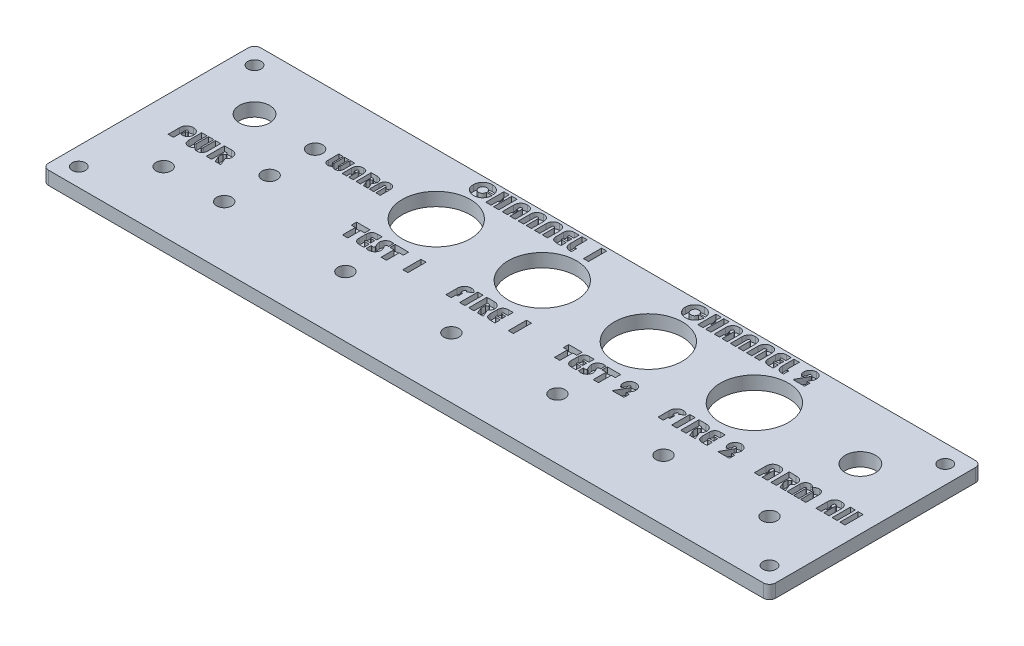
SolidWorks part; units mm, degrees
ref_plane "Front Plane" through (0, 0, 0) normal (0, 0, 1) x (1, 0, 0)
ref_plane "Top Plane" through (0, 0, 0) normal (0, 1, 0) x (1, 0, 0)
ref_plane "Right Plane" through (0, 0, 0) normal (1, 0, 0) x (0, 0, -1)
sketch "face" plane through (0, 0, 0) normal (0, 1, 0) x (1, 0, 0)
  line L0 (152.4, 88.9) -> (152.4, 0) construction
  line L1 (0, 0) -> (304.8, 0)
  line L2 (0, 0) -> (0, 88.9)
  line L3 (0, 88.9) -> (304.8, 88.9)
  line L4 (304.8, 0) -> (304.8, 88.9)
  line L5 (0, 44.45) -> (304.8, 44.45) construction
  line L6 (234.95, 63.5) -> (234.95, 25.4) construction
  line L7 (25.4, 63.5) -> (25.4, 25.4) construction
  line L8 (279.4, 63.5) -> (279.4, 25.4) construction
  line L12 (279.4, 63.5) -> (234.95, 63.5) construction
  line L13 (279.4, 63.5) -> (25.4, 63.5) construction
  line L14 (50.8, 63.5) -> (50.8, 25.4) construction
  circle A0 centre (7.62, 81.28) radius 2.794
  circle A12 centre (297.18, 81.28) radius 2.794
  circle A13 centre (297.18, 7.62) radius 2.794
  circle A14 centre (7.62, 7.62) radius 2.794
  circle A26 centre (234.95, 63.5) radius 14.2875
  circle A31 centre (234.95, 25.4) radius 3.175
  circle A40 centre (279.4, 63.5) radius 6.35
  circle A41 centre (279.4, 25.4) radius 3.175
  circle A45 centre (25.4, 63.5) radius 6.35
  circle A46 centre (25.4, 25.4) radius 3.175
  circle A48 centre (190.5, 63.5) radius 14.2875
  circle A49 centre (190.5, 25.4) radius 3.175
  circle A50 centre (146.05, 63.5) radius 14.2875
  circle A51 centre (146.05, 25.4) radius 3.175
  circle A52 centre (101.6, 63.5) radius 14.2875
  circle A53 centre (101.6, 25.4) radius 3.175
  circle A54 centre (50.8, 63.5) radius 3.175
  circle A55 centre (50.8, 25.4) radius 3.175
  circle A56 centre (50.8, 44.45) radius 3.175
  point P11 (279.4, 44.45)
  point P22 (25.4, 44.45)
  dimension "D3" = 5.588
  dimension "D6" = 12.7
  dimension "D7" = 6.35
  dimension "D11" = 44.45
  dimension "D16" = 28.575
  dimension "D21" = 6.35
  dimension "D9" = 25.4
  dimension "D12" = 6.35
  dimension "D13" = 12.7
  dimension "D14" = 6.35
  dimension "D18" = 6.35
  dimension "D19" = 6.35
  dimension "D1" = 304.8
  dimension "D2" = 88.9
  dimension "D4" = 7.62
  dimension "D5" = 7.62
  dimension "D8" = 38.1
  dimension "D10" = 44.45
  dimension "D15" = 25.4
  dimension "D17" = 25.4
extrude "face_cut" add sketch "face" along normal blind 5.588 contours L1 L4 L3 L2 A12 A40 A41 A0 A13 A14 region at (151.0156, 0, -42.3544)
fillet "Fillet1" radius 2.54 4 edges at (0, 2.794, -88.9) (0, 2.794, 0) (304.8, 2.794, 0) (304.8, 2.794, -88.9)
sketch "Sketch1" plane through (0, 5.588, 0) normal (0, 1, 0) x (1, 0, 0)
  line L0 (92.075, 80.01) -> (155.575, 80.01) construction
  line L1 (146.05, 63.5) -> (101.6, 63.5) construction
  line L2 (123.825, 63.5) -> (123.825, 80.01) construction
  line L3 (234.95, 63.5) -> (190.5, 63.5) construction
  line L4 (212.725, 63.5) -> (212.725, 80.01) construction
  line L5 (180.975, 80.01) -> (244.475, 80.01) construction
  line L6 (279.4, 63.5) -> (279.4, 38.1) construction
  line L7 (259.3255, 38.1) -> (299.4745, 38.1) construction
  line L8 (82.55, 38.1) -> (120.65, 38.1) construction
  line L9 (101.6, 63.5) -> (101.6, 38.1) construction
  line L10 (127, 38.1) -> (165.1, 38.1) construction
  line L11 (146.05, 63.5) -> (146.05, 38.1) construction
  line L12 (171.45, 38.1) -> (209.55, 38.1) construction
  line L13 (190.5, 63.5) -> (190.5, 38.1) construction
  line L14 (234.95, 63.5) -> (234.95, 38.1) construction
  line L15 (215.9, 38.1) -> (254, 38.1) construction
  line L16 (0, 38.1) -> (50.8, 38.1) construction
  line L17 (25.4, 63.5) -> (25.4, 38.1) construction
  line L18 (56.3957, 60.365) -> (82.55, 60.365) construction
  text T0 "CHANNEL 1" font "Blippo" height 7.62
  text T1 "CHANNEL 2" font "Blippo" height 7.62
  text T2 "ARM All" font "Blippo" height 7.62
  text T3 "TEST 1" font "Blippo" height 7.62
  text T4 "FIRE 1" font "Blippo" height 7.62
  text T5 "TEST 2" font "Blippo" height 7.62
  text T6 "FIRE 2" font "Blippo" height 7.62
  text T7 "PWR" font "Blippo" height 7.62
  text T8 "WARN" font "Blippo" height 6.35
  dimension "D1" = 16.51
  dimension "D2" = 63.5
  dimension "D3" = 16.51
  dimension "D4" = 63.5
  dimension "D5" = 25.4
  dimension "D6" = 25.4
  dimension "D7" = 38.1
  dimension "D8" = 25.4
  dimension "D9" = 50.8
extrude "Cut-Extrude1" cut sketch "Sketch1" against normal blind 2.54
